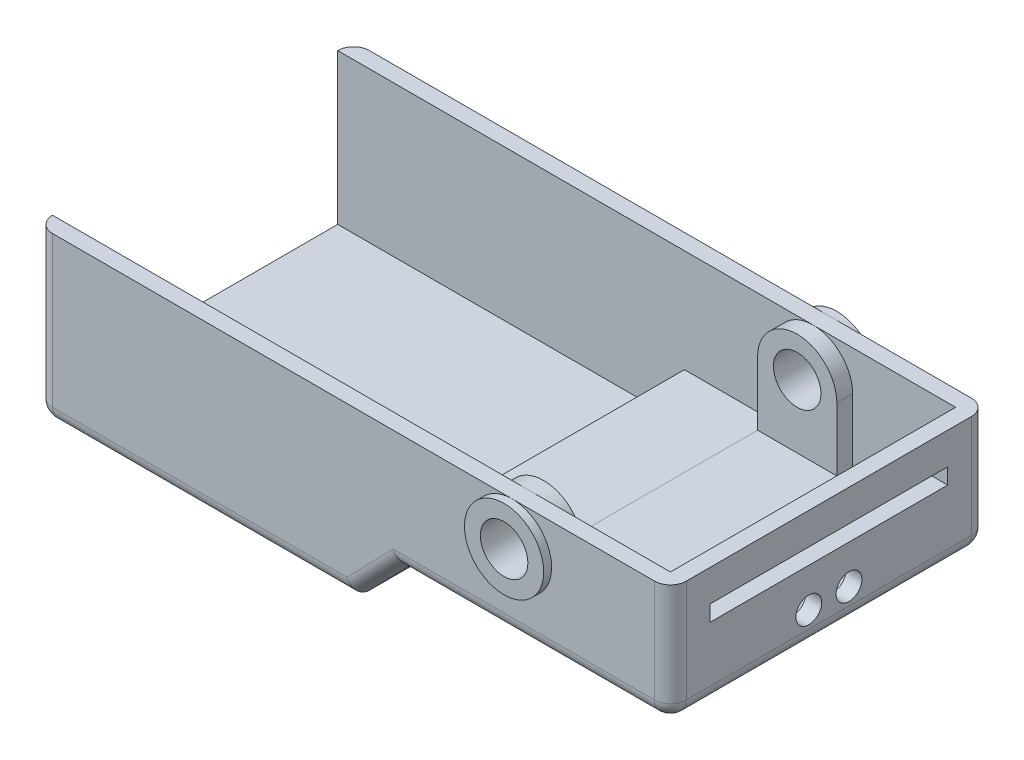
SolidWorks part; units mm, degrees
ref_plane "Front Plane" through (0, 0, 0) normal (0, 0, 1) x (1, 0, 0)
ref_plane "Top Plane" through (0, 0, 0) normal (0, 1, 0) x (1, 0, 0)
ref_plane "Right Plane" through (0, 0, 0) normal (1, 0, 0) x (0, 0, -1)
sketch "Sketch1" plane through (0, 0, 0) normal (0, 0, 1) x (1, 0, 0)
  circle A0 centre (0, 0) radius 15
  circle A1 centre (0, 0) radius 25
extrude "Boss-Extrude1" add sketch "Sketch1" against normal blind 25
sketch "Sketch2" plane through (0, 0, 0) normal (0, 0, 1) x (1, 0, 0)
  line L0 (0, -42.5582) -> (0, -80) construction
  line L1 (0, -80) -> (100, -80) construction
  line L2 (0, -80) -> (-300, -80) construction
  line L5 (-70.8728, -50) -> (100, -50)
  line L6 (0, 25) -> (100, 25) construction
  line L7 (100, 25) -> (100, -50)
  line L8 (100, 25) -> (90, 25)
  line L9 (90, 25) -> (90, -40)
  line L10 (90, -40) -> (25, -40)
  line L11 (-300, -80) -> (-100, -80)
  line L12 (-100, -80) -> (-70.8728, -50)
  line L13 (-300, -80) -> (-300, -70)
  line L14 (-300, -70) -> (-110.2996, -70)
  line L15 (-110.2996, -70) -> (-81.1724, -40)
  line L16 (-25, 0) -> (-25, -40)
  line L17 (25, 0) -> (25, -40)
  line L18 (-25, -40) -> (-81.1724, -40)
  circle A0 centre (0, 0) radius 25 construction
  arc A1 (-25, 0) -> (25, 0) centre (0, 0) ccw
ref_plane "Plane1" through (0, 0, -25) normal (0, 0, -1) x (-1, 0, 0)
sketch "Sketch3" plane through (0, 0, -25) normal (0, 0, -1) x (-1, 0, 0)
  line L13 (-25, 0) -> (-25, -40)
  line L14 (25, -40) -> (25, 0)
  line L15 (81.1724, -40) -> (25, -40)
  line L16 (110.2996, -70) -> (81.1724, -40)
  line L17 (300, -70) -> (110.2996, -70)
  line L18 (300, -80) -> (300, -70)
  line L19 (100, -80) -> (300, -80)
  line L20 (70.8728, -50) -> (100, -80)
  line L21 (-100, -50) -> (70.8728, -50)
  line L22 (-100, 25) -> (-100, -50)
  line L23 (-90, 25) -> (-100, 25)
  line L24 (-90, -40) -> (-90, 25)
  line L25 (-25, -40) -> (-90, -40)
  line L26 (-25, 0) -> (-25, -40)
  line L27 (25, -40) -> (25, 0)
  line L28 (81.1724, -40) -> (25, -40)
  line L29 (110.2996, -70) -> (81.1724, -40)
  line L30 (300, -70) -> (110.2996, -70)
  line L31 (300, -80) -> (300, -70)
  line L32 (100, -80) -> (300, -80)
  line L33 (70.8728, -50) -> (100, -80)
  line L34 (-100, -50) -> (70.8728, -50)
  line L35 (-100, 25) -> (-100, -50)
  line L36 (-90, 25) -> (-100, 25)
  line L37 (-90, -40) -> (-90, 25)
  line L38 (-25, -40) -> (-90, -40)
  arc A1 (-25, 0) -> (25, 0) centre (0, 0) ccw
  arc A2 (-25, 0) -> (25, 0) centre (0, 0) ccw
  dimension "D1" = 0
extrude "Boss-Extrude2" add sketch "Sketch3" against normal blind 20
ref_plane "Plane3" through (0, 0, -185) normal (0, 0, -1) x (-1, 0, 0)
sketch "Sketch4" plane through (0, 0, -185) normal (0, 0, -1) x (-1, 0, 0)
  circle A1 centre (0, 0) radius 25
  circle A2 centre (0, 0) radius 25
  circle A3 centre (0, 0) radius 15
  circle A4 centre (0, 0) radius 15
  dimension "D1" = 0
  dimension "D2" = 0
extrude "Boss-Extrude3" add sketch "Sketch4" along normal blind 25 separate body
sketch "Sketch5" plane through (0, 0, -185) normal (0, 0, -1) x (-1, 0, 0)
  line L13 (70.8728, -50) -> (100, -80)
  line L14 (-100, -50) -> (70.8728, -50)
  line L15 (-100, 25) -> (-100, -50)
  line L16 (-90, 25) -> (-100, 25)
  line L17 (-90, -40) -> (-90, 25)
  line L18 (-25, -40) -> (-90, -40)
  line L19 (-25, 0) -> (-25, -40)
  line L20 (25, -40) -> (25, 0)
  line L21 (81.1724, -40) -> (25, -40)
  line L22 (110.2996, -70) -> (81.1724, -40)
  line L23 (300, -70) -> (110.2996, -70)
  line L24 (300, -80) -> (300, -70)
  line L25 (100, -80) -> (300, -80)
  line L26 (70.8728, -50) -> (100, -80)
  line L27 (-100, -50) -> (70.8728, -50)
  line L28 (-100, 25) -> (-100, -50)
  line L29 (-90, 25) -> (-100, 25)
  line L30 (-90, -40) -> (-90, 25)
  line L31 (-25, -40) -> (-90, -40)
  line L32 (-25, 0) -> (-25, -40)
  line L33 (25, -40) -> (25, 0)
  line L34 (81.1724, -40) -> (25, -40)
  line L35 (110.2996, -70) -> (81.1724, -40)
  line L36 (300, -70) -> (110.2996, -70)
  line L37 (300, -80) -> (300, -70)
  line L38 (100, -80) -> (300, -80)
  arc A1 (-25, 0) -> (25, 0) centre (0, 0) ccw
  arc A2 (-25, 0) -> (25, 0) centre (0, 0) ccw
  dimension "D1" = 0
extrude "Boss-Extrude4" add sketch "Sketch5" along normal blind 20
sketch "Sketch6" plane through (100, 0, 0) normal (1, 0, 0) x (0, 0, -1)
  line L0 (25, 25) -> (185, 25)
  line L1 (185, 25) -> (185, 5)
  line L2 (185, -57.75) -> (185, 57.75) construction
  line L3 (185, 5) -> (25, 5)
  line L4 (25, 25) -> (25, -50) construction
  line L5 (25, 25) -> (25, 5)
extrude "Boss-Extrude5" add sketch "Sketch6" against normal blind 10
sketch "Sketch7" plane through (0, 0, -25) normal (0, 0, -1) x (-1, 0, 0)
  line L0 (-90, -40) -> (-100, -40)
  line L1 (25, -40) -> (-25, -40)
  line L13 (-25, 0) -> (-25, -40)
  line L14 (25, -40) -> (25, 0)
  line L15 (81.1724, -40) -> (25, -40)
  line L16 (110.2996, -70) -> (81.1724, -40)
  line L17 (300, -70) -> (110.2996, -70)
  line L18 (300, -80) -> (300, -70)
  line L19 (100, -80) -> (300, -80)
  line L20 (70.8728, -50) -> (100, -80)
  line L21 (-100, -50) -> (70.8728, -50)
  line L22 (-100, 25) -> (-100, -50)
  line L23 (-90, 25) -> (-100, 25)
  line L24 (-90, -40) -> (-90, 25)
  line L25 (-25, -40) -> (-90, -40)
  line L28 (81.1724, -40) -> (25, -40)
  line L29 (110.2996, -70) -> (81.1724, -40)
  line L30 (300, -70) -> (110.2996, -70)
  line L31 (300, -80) -> (300, -70)
  line L32 (100, -80) -> (300, -80)
  line L33 (70.8728, -50) -> (100, -80)
  line L34 (-100, -50) -> (70.8728, -50)
  line L35 (-100, -40) -> (-100, -50)
  line L38 (-25, -40) -> (-90, -40)
  arc A1 (-25, 0) -> (25, 0) centre (0, 0) ccw
  dimension "D1" = 0
extrude "Boss-Extrude6" add sketch "Sketch7" along normal up to next
sketch "Sketch8" plane through (0, 0, -205) normal (0, 0, -1) x (-1, 0, 0)
  line L0 (-90, 25) -> (-90, -40)
  line L1 (-90, -40) -> (-25, -40)
  line L2 (-25, -40) -> (-25, 0)
  line L3 (25, 0) -> (25, -40)
  line L4 (25, -40) -> (81.1724, -40)
  line L5 (81.1724, -40) -> (110.2996, -70)
  line L6 (110.2996, -70) -> (300, -70)
  line L7 (300, -70) -> (300, 25)
  line L8 (300, 25) -> (-90, 25)
  arc A0 (25, 0) -> (-25, 0) centre (0, 0) ccw
  line M5 (300, -70) -> (110.2996, -70)
  line M6 (110.2996, -70) -> (81.1724, -40)
  line M7 (81.1724, -40) -> (25, -40)
  line M8 (25, -40) -> (25, 0)
  line M10 (-25, 0) -> (-25, -40)
  line M11 (-25, -40) -> (-90, -40)
  line M12 (-90, -40) -> (-90, 25)
extrude "Boss-Extrude7" add sketch "Sketch8" against normal blind 10 contours A0 L8 M12 M11 M10 | A0 L7 L8 M8 M7 M6 M5 region at (56.3282, -6.6718, -205) region at (-170.6402, -19.3192, -205)
sketch "Sketch9" plane through (0, 0, -25) normal (0, 0, -1) x (-1, 0, 0)
  line L9 (-90, 25) -> (-90, -40)
  line L10 (-90, -40) -> (-25, -40)
  line L11 (-25, -40) -> (-25, 0)
  line L12 (-90, 25) -> (300, 25)
  line L13 (300, 25) -> (300, -70)
  line L14 (300, -70) -> (110.2996, -70)
  line L15 (110.2996, -70) -> (81.1724, -40)
  line L16 (81.1724, -40) -> (25, -40)
  line L17 (25, -40) -> (25, 0)
  arc A1 (25, 0) -> (-25, 0) centre (0, 0) ccw
sketch "Sketch10" plane through (0, 0, -5) normal (0, 0, 1) x (1, 0, 0)
  line L7 (-300, 25) -> (-300, -70) construction
  line L9 (-300, 25) -> (-300, -70)
  line L10 (-300, -70) -> (-110.2996, -70) construction
  line L11 (-300, -70) -> (-110.2996, -70)
  line L12 (90, 25) -> (-300, 25) construction
  line L13 (90, 25) -> (-300, 25)
  line L14 (-110.2996, -70) -> (-81.1724, -40) construction
  line L15 (-25, -40) -> (-81.1724, -40) construction
  line L16 (-25, 0) -> (-25, -40) construction
  line L17 (-25, 0) -> (-25, -40)
  line L18 (-25, -40) -> (-81.1724, -40)
  line L19 (-110.2996, -70) -> (-81.1724, -40)
  line L20 (-300, -70) -> (-110.2996, -70)
  line L21 (-81.1724, -40) -> (-25, -40)
  line L22 (90, 25) -> (90, -40)
  line L23 (90, -40) -> (25, -40)
  line L24 (25, -40) -> (25, 0)
  arc A1 (25, 0) -> (-25, 0) centre (0, 0) ccw
  line M3 (-25, 0) -> (-25, -40)
  line M4 (-25, -40) -> (-81.1724, -40)
  line M5 (-81.1724, -40) -> (-110.2996, -70)
  line M6 (-110.2996, -70) -> (-300, -70)
  line M13 (90, 25) -> (90, -40)
  line M14 (90, -40) -> (25, -40)
  line M15 (25, -40) -> (25, 0)
extrude "Boss-Extrude8" add sketch "Sketch10" against normal blind 10 contours A1 L13 L9 M6 M5 M4 M3 | A1 L13 M15 M14 M13 region at (-170.6402, -19.3192, -5) region at (56.3282, -6.6718, -5)
fillet "Fillet1" radius 10 12 edges at (-300, -27.5, -205) (-300, -27.5, -5) (-300, -80, -105) (-200, -80, -205) (-85.4364, -65, -205) (14.5636, -50, -205) (100, -12.5, -205) (100, -12.5, -5) (100, -50, -105) (14.5636, -50, -5) (-85.4364, -65, -5) (-200, -80, -5)
sketch "Sketch12" plane through (100, 0, 0) normal (1, 0, 0) x (0, 0, -1)
  line L1 (25, 5) -> (185, 5)
  line L2 (25, 5) -> (25, -40)
  line L3 (25, -40) -> (185, -40)
  line L4 (185, 5) -> (185, -40)
extrude "Boss-Extrude9" add sketch "Sketch12" against normal blind 10
sketch "Sketch14" plane through (90, 0, 0) normal (-1, 0, 0) x (0, 0, 1)
  line L0 (-105, -40) -> (-105, -18.7) construction
  line L1 (-195, -40) -> (-15, -40) construction
  line L2 (-105, -29.35) -> (-120.8144, -29.35) construction
  line L3 (-127.85, -40) -> (-82.15, -40) construction
  line L4 (-127.85, -40) -> (-127.85, -18.7) construction
  line L5 (-127.85, -18.7) -> (-82.15, -18.7) construction
  line L6 (-82.15, -40) -> (-82.15, -18.7) construction
  line L7 (-127.85, -40) -> (-82.15, -18.7) construction
  line L8 (-127.85, -18.7) -> (-82.15, -40) construction
  circle A0 centre (-125.35, -21.2) radius 1.55
  circle A1 centre (-125.35, -21.2) radius 2.5 construction
  circle A2 centre (-125.35, -37.5) radius 1.55
  circle A3 centre (-125.35, -37.5) radius 2.5 construction
  circle A4 centre (-84.65, -37.5) radius 2.5 construction
  circle A5 centre (-84.65, -37.5) radius 1.55
  circle A6 centre (-84.65, -21.2) radius 2.5 construction
  circle A7 centre (-84.65, -21.2) radius 1.55
  point P4 (-105, -29.35)
  dimension "D2" = 2.5
  dimension "D1" = 21.3
  dimension "D3" = 2.5
extrude "Cut-Extrude2" cut sketch "Sketch14" against normal blind 3 contours A2 | A5 | A7 | A0 region at (90, -37.5, -125.35) region at (90, -37.5, -84.65) region at (90, -21.2, -84.65)
sketch "Sketch15" plane through (90, 0, 0) normal (-1, 0, 0) x (0, 0, 1)
  line L0 (-105, -29.35) -> (-125.85, -29.35) construction
  line L1 (-105, -40) -> (-105, -18.7) construction
  line L2 (-105, -29.35) -> (-105, -24.7653) construction
  circle A0 centre (-117.7, -29.35) radius 8.15
  circle A1 centre (-92.3, -29.35) radius 8.15
  dimension "D2" = 16.3
  dimension "D1" = 20.85
extrude "Cut-Extrude3" cut sketch "Sketch15" against normal through all
sketch "Sketch16" plane through (100, 0, 0) normal (1, 0, 0) x (0, 0, -1)
  line L0 (105, -40) -> (105, 0) construction
  line L1 (195, -40) -> (15, -40) construction
  line L3 (30, -5) -> (180, -5)
  line L4 (30, -5) -> (30, 5)
  line L5 (30, 5) -> (180, 5)
  line L6 (180, -5) -> (180, 5)
  line L7 (30, -5) -> (180, 5) construction
  line L8 (30, 5) -> (180, -5) construction
extrude "Cut-Extrude4" cut sketch "Sketch16" against normal blind 10
